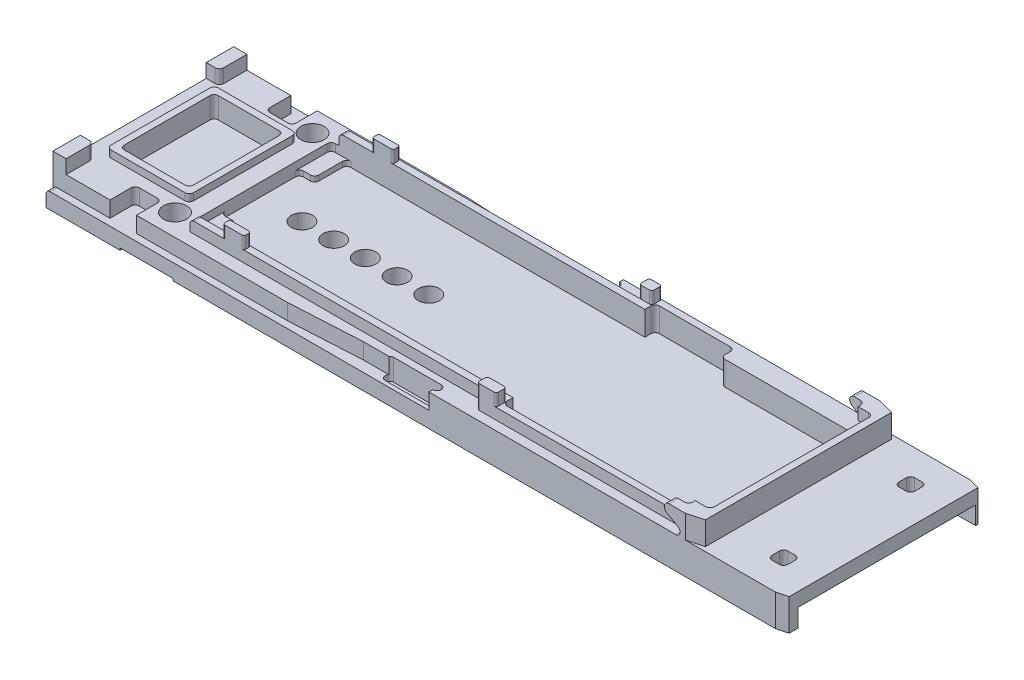
SolidWorks part; units mm, degrees
material "6063-T5"
ref_plane "Front Plane" through (0, 0, 0) normal (0, 0, 1) x (1, 0, 0)
ref_plane "Top Plane" through (0, 0, 0) normal (0, 1, 0) x (1, 0, 0)
ref_plane "Right Plane" through (0, 0, 0) normal (1, 0, 0) x (0, 0, -1)
sketch "Sketch1" plane through (0, 0, 0) normal (0, 1, 0) x (1, 0, 0)
  line L1 (-35, 9.2) -> (35, 9.2)
  line L2 (-35, 9.2) -> (-35, -9.2)
  line L3 (-35, -9.2) -> (35, -9.2)
  line L4 (35, 9.2) -> (35, -9.2)
  line L5 (-35, 9.2) -> (35, -9.2) construction
  line L6 (-35, -9.2) -> (35, 9.2) construction
  point P0 (0, 0)
  dimension "D1" = 70
  dimension "D2" = 18.4
extrude "Boss-Extrude1" add sketch "Sketch1" along normal blind 4.05
sketch "Sketch2" plane through (0, 4.05, 0) normal (0, 1, 0) x (1, 0, 0)
  line L0 (-35, 9.2) -> (-35, -9.2) construction
  line L1 (-23.95, 6.725) -> (-23.95, -6.725)
  line L2 (-23.95, -6.725) -> (6.7, -6.725)
  line L3 (6.7, -6.725) -> (6.7, -7.7)
  line L4 (6.7, -7.7) -> (26.3, -7.7)
  line L6 (26.3, -7.7) -> (26.3, 7.7)
  line L7 (26.3, 7.7) -> (5.7, 7.7)
  line L8 (5.7, 7.7) -> (5.7, 6.725)
  line L9 (5.7, 6.725) -> (-23.95, 6.725)
  line L10 (0, 0) -> (26.3, 0) construction
  dimension "D1" = 13.45
  dimension "D2" = 15.4
  dimension "D3" = 20.6
  dimension "D4" = 50.25
  dimension "D5" = 11.05
  dimension "D6" = 19.6
extrude "Cut-Extrude1" cut sketch "Sketch2" against normal blind 2.28
sketch "Sketch5" plane through (0, 4.05, 0) normal (0, 1, 0) x (1, 0, 0)
  line L0 (-23.95, 0) -> (-35, 0) construction
  line L1 (-32.75, 4.45) -> (-26.2, 4.45)
  line L2 (-32.75, 4.45) -> (-32.75, -4.45)
  line L3 (-32.75, -4.45) -> (-26.2, -4.45)
  line L4 (-26.2, 4.45) -> (-26.2, -4.45)
  line L5 (-32.75, 4.45) -> (-26.2, -4.45) construction
  line L6 (-32.75, -4.45) -> (-26.2, 4.45) construction
  line L7 (-23.95, 6.725) -> (-23.95, -6.725) construction
  line L8 (-35, 9.2) -> (-35, -9.2) construction
  point P0 (-29.475, 0)
  dimension "D1" = 8.9
  dimension "D2" = 6.55
extrude "Cut-Extrude2" cut sketch "Sketch5" against normal blind 2.38
sketch "Sketch17" plane through (0, 4.05, 0) normal (0, 1, 0) x (1, 0, 0)
  line L0 (-35, -9.2) -> (35, -9.2) construction
  line L1 (35, 9.2) -> (35, -9.2)
  line L2 (0, 0) -> (26.95, 0) construction
  line L4 (26.3, -7.7) -> (26.3, 7.7) construction
  line L5 (5.7, 7.7) -> (5.7, 6.725) construction
  line L11 (-35, 9.2) -> (35, 9.2)
  line L12 (-35, 9.2) -> (-35, -9.2)
  line L13 (-35, -9.2) -> (35, -9.2)
  line L14 (-23.2, 7.375) -> (-23.2, -7.375)
  line L57 (-23.2, -7.375) -> (5.05, -7.375)
  line L58 (5.05, -7.375) -> (5.05, -8.325)
  line L59 (5.05, -8.325) -> (26.95, -8.325)
  line L60 (26.95, -8.325) -> (26.95, 8.325)
  line L61 (26.95, 8.325) -> (5.05, 8.325)
  line L62 (5.05, 8.325) -> (5.05, 7.375)
  line L63 (5.05, 7.375) -> (-23.2, 7.375)
  dimension "D1" = 11.8
  dimension "D2" = 7.375
  dimension "D3" = 8.325
  dimension "D4" = 0.65
  dimension "D5" = 0.65
extrude "Cut-Extrude8" cut sketch "Sketch17" against normal blind 1.05
sketch "Sketch18" plane through (0, 0, 0) normal (0, 1, 0) x (1, 0, 0)
  line L10 (-32.75, 4.45) -> (-26.2, 4.45) construction
  line L11 (-26.2, -4.45) -> (-26.2, 4.45) construction
  line L12 (-32.75, -4.45) -> (-26.2, -4.45) construction
  line L13 (-32.75, 4.45) -> (-32.75, -4.45) construction
  line L14 (-33.375, 5.075) -> (-33.375, -5.075)
  line L15 (-33.375, -5.075) -> (-25.575, -5.075)
  line L16 (-25.575, -5.075) -> (-25.575, 5.075)
  line L17 (-25.575, 5.075) -> (-33.375, 5.075)
  line L18 (-33.375, 5.075) -> (-33.375, -5.075)
  line L19 (-33.375, -5.075) -> (-25.575, -5.075)
  line L20 (-25.575, -5.075) -> (-25.575, 5.075)
  line L21 (-25.575, 5.075) -> (-33.375, 5.075)
  line L22 (-32.75, 4.45) -> (-26.2, 4.45)
  line L23 (-26.2, -4.45) -> (-26.2, 4.45)
  line L24 (-32.75, -4.45) -> (-26.2, -4.45)
  line L25 (-32.75, 4.45) -> (-32.75, -4.45)
  dimension "D1" = 0.625
extrude "Boss-Extrude3" add sketch "Sketch18" along normal blind 3.67
hole_wizard "CSK for M2 Countersunk Flat Head Screw1" positions "Sketch7" profile "Sketch6" countersink size "M2" standard "ISO" end condition through all
sketch "Sketch7" plane through (-7.9019, 0, 3.8056) normal (0, 1, 0) x (-1, 0, 0)
  line L0 (-7.9019, -3.8056) -> (27.0981, -3.8056) construction
  line L1 (27.0981, -13.0056) -> (27.0981, 5.3944) construction
  line L4 (27.0981, 5.3944) -> (27.0981, -13.0056) construction
  point P0 (17.5981, -10.3056)
  point P1 (17.5981, 2.6944)
  dimension "D1" = 13
  dimension "D2" = 9.5
sketch "Sketch6" plane through (-25.5, 0, -6.5) normal (1, 0, 0) x (0, 0, -1)
  line L0 (0, 0) -> (0, 4.05)
  line L1 (0, 4.05) -> (1.1, 4.05)
  line L2 (1.1, 4.05) -> (1.1, 1.3)
  line L3 (1.1, 1.3) -> (2.2, 0.2)
  line L4 (2.2, 0.2) -> (2.2, 0)
  line L6 (2.2, 0) -> (0, 0)
  line L7 (-1.1, 1.3) -> (-2.2, 0.2) construction
  line L11 (0, -6.35) -> (0, 107.95) construction
  dimension "Thru Hole Dia." = 2.2
  dimension "Thru Hole Depth" = 4.05
  dimension "C'Sink Dia." = 4.4
  dimension "C'Sink Angle" = 90
  dimension "Head Clearance" = 0.2
sketch "Sketch13" plane through (0, 4.05, 0) normal (0, 1, 0) x (1, 0, 0)
  line L0 (-35, 9.2) -> (1.2, 9.2)
  line L1 (35, 9.2) -> (35, -9.2) construction
  line L2 (1.2, 9.2) -> (1.2, 8.175)
  line L3 (1.2, 8.175) -> (-6, 8.175)
  line L4 (-6, 8.175) -> (-12.8, 8.55)
  line L5 (-12.8, 8.55) -> (-35, 8.55)
  line L6 (-35, 8.55) -> (-35, 9.2)
  line L10 (35, 9.2) -> (-35, 9.2) construction
  line L11 (-35, 9.2) -> (-35, -9.2) construction
  dimension "D1" = 8.175
  dimension "D2" = 33.8
  dimension "D3" = 7.2
  dimension "D4" = 6.8
  dimension "D5" = 0.65
extrude "Cut-Extrude5" cut sketch "Sketch13" against normal offset from surface (2.55 mm away) 1.5 up to face at (-25.5, 0, -8.7)
sketch "Sketch19" plane through (0, 0, 0) normal (0, 1, 0) x (1, 0, 0)
  line L1 (-35, 8.55) -> (-33.75, 8.55)
  line L2 (-35, 8.55) -> (-35, 5.95)
  line L3 (-35, 5.95) -> (-33.75, 5.95)
  line L4 (-33.75, 8.55) -> (-33.75, 5.95)
  dimension "D1" = 2.6
  dimension "D2" = 1.25
extrude "Boss-Extrude4" add sketch "Sketch19" along normal blind 4.3
sketch "Sketch20" plane through (0, 3, 0) normal (0, 1, 0) x (1, 0, 0)
  line L0 (-33.75, 8.55) -> (-12.8, 8.55) construction
  line L1 (-29.6, 8.55) -> (-27.1, 8.55)
  line L2 (-29.6, 8.55) -> (-29.6, 6.165)
  line L3 (-29.6, 6.165) -> (-27.1, 6.165)
  line L4 (-27.1, 8.55) -> (-27.1, 6.165)
  line L5 (-35, -9.2) -> (-35, 5.95) construction
  dimension "D1" = 2.5
  dimension "D2" = 6.165
  dimension "D3" = 5.4
extrude "Cut-Extrude9" cut sketch "Sketch20" against normal up to surface (1.5 mm away) up to face at (-14.4, 1.5, -8.6417)
sketch "Sketch21" plane through (0, 0, 0) normal (0, 1, 0) x (1, 0, 0)
  line L0 (5.05, 7.375) -> (-23.2, 7.375) construction
  line L1 (-20.1, 7.375) -> (-18.1, 7.375)
  line L2 (-20.1, 7.375) -> (-20.1, 6.725)
  line L3 (-20.1, 6.725) -> (-18.1, 6.725)
  line L4 (-18.1, 7.375) -> (-18.1, 6.725)
  line L5 (5.7, 6.725) -> (-23.95, 6.725) construction
  line L6 (-23.2, 7.375) -> (-23.2, 6.725) construction
  dimension "D1" = 2
  dimension "D2" = 5.1
extrude "Boss-Extrude5" add sketch "Sketch21" along normal blind 5.2
sketch "Sketch22" plane through (0, 0, 0) normal (0, -1, 0) x (1, 0, 0)
  line L0 (24.9, -7.7) -> (26.95, -7.7)
  line L1 (26.3, -7.7) -> (5.7, -7.7) construction
  line L2 (26.95, -8.325) -> (26.95, 8.325) construction
  line L3 (26.95, -7.7) -> (26.95, -9.2)
  line L4 (1.2, -9.2) -> (35, -9.2) construction
  line L5 (26.95, -9.2) -> (22.15, -9.2)
  line L6 (22.15, -9.2) -> (22.15, -8.325)
  line L7 (5.05, -8.325) -> (26.95, -8.325) construction
  line L8 (22.15, -8.325) -> (24.9, -8.325)
  line L9 (24.9, -8.325) -> (24.9, -7.7)
  dimension "D1" = 4.8
  dimension "D2" = 2.05
extrude "Boss-Extrude6" add sketch "Sketch22" against normal blind 5.2
chamfer "Chamfer2" distance 1.5 angle 15 1 edges at (26.95, 4.1, -9.2)
chamfer "Chamfer1" distance 1 angle 15 2 edges at (35, 1.5, -9.2) (35, 1.5, 9.2)
sketch "Sketch25" plane through (0, 3, 0) normal (0, 1, 0) x (1, 0, 0)
  line L1 (31.2, 6.75) -> (31.9, 6.75)
  line L2 (30.8, 6.35) -> (30.8, 5.65)
  line L3 (31.2, 5.25) -> (31.9, 5.25)
  line L4 (32.3, 6.35) -> (32.3, 5.65)
  line L5 (30.8, 6.75) -> (32.3, 5.25) construction
  line L6 (30.8, 5.25) -> (32.3, 6.75) construction
  line L7 (35, -8.9321) -> (35, 8.9321) construction
  arc A0 (31.9, 6.75) -> (32.3, 6.35) centre (31.9, 6.35) cw
  arc A1 (32.3, 5.65) -> (31.9, 5.25) centre (31.9, 5.65) cw
  arc A2 (31.2, 5.25) -> (30.8, 5.65) centre (31.2, 5.65) cw
  arc A3 (30.8, 6.35) -> (31.2, 6.75) centre (31.2, 6.35) cw
  point P0 (31.55, 6)
  dimension "D5" = 0.4
  dimension "D1" = 1.5
  dimension "D2" = 1.5
  dimension "D3" = 6
  dimension "D4" = 4.2
extrude "Cut-Extrude10" cut sketch "Sketch25" against normal through all
sketch "Sketch16" plane through (0, 0, 0) normal (0, -1, 0) x (1, 0, 0)
  line L0 (-28, -9.2) -> (-28, -6.5)
  line L2 (-23, -6.5) -> (-23, -9.2)
  line L3 (-23, -9.2) -> (-28, -9.2)
  line L4 (34, -9.2) -> (-35, -9.2) construction
  arc A0 (-28, -6.5) -> (-23, -6.5) centre (-25.5, -6.5) cw
  circle A1 centre (-25.5, -6.5) radius 2.2 construction
  dimension "D1" = 5
extrude "Cut-Extrude7" cut sketch "Sketch16" against normal blind 0.2
mirror "Mirror1" about plane through (0, 0, 0) normal (0, 0, 1) of "Cut-Extrude10", "Boss-Extrude5", "Cut-Extrude9", "Boss-Extrude4", "Cut-Extrude5", "Cut-Extrude7", "Boss-Extrude6", "Chamfer2"
sketch "Sketch29" plane through (0, 0, -9.2) normal (0, 0, 1) x (1, 0, 0)
  line L0 (23.6939, 4.3603) -> (24.7572, 3.7464)
  line L1 (24.6572, 3.7464) -> (23.6689, 4.317) construction
  line L2 (24.5572, 3) -> (21.5572, 3)
  line L3 (34, 3) -> (25.45, 3) construction
  line L5 (22.15, 5.2) -> (25.45, 5.2) construction
  line L6 (23.9189, 5.2) -> (21.5572, 5.2)
  line L7 (21.5572, 5.2) -> (21.5572, 3)
  arc A0 (24.7572, 3.7464) -> (24.5572, 3) centre (24.5572, 3.4) cw
  arc A1 (23.6939, 4.3603) -> (23.9189, 5.2) centre (23.9189, 4.75) cw
  arc A2 (23.9189, 5.25) -> (23.6689, 4.317) centre (23.9189, 4.75) ccw construction
  dimension "D2" = 3
  dimension "D1" = 0.4
extrude "Cut-Extrude12" cut sketch "Sketch29" along normal up to surface (0.875 mm away) up to face at (23.525, 4.625, -8.325)
sketch "Sketch30" plane through (0, 0, 9.2) normal (0, 0, 1) x (1, 0, 0)
  line L0 (23.6939, 4.3603) -> (24.7572, 3.7464)
  line L1 (24.5572, 3) -> (21.5572, 3)
  line L2 (22.15, 5.2) -> (25.45, 5.2) construction
  line L3 (23.9189, 5.2) -> (21.5572, 5.2)
  line L4 (21.5572, 5.2) -> (21.5572, 3)
  line L6 (1.2, 3) -> (22.15, 3) construction
  line L7 (24.7572, 3.7464) -> (24.2313, 4.05) construction
  arc A0 (24.7572, 3.7464) -> (24.5572, 3) centre (24.5572, 3.4) cw
  arc A1 (23.9189, 5.2) -> (23.6939, 4.3603) centre (23.9189, 4.75) ccw construction
  arc A2 (23.6939, 4.3603) -> (23.9189, 5.2) centre (23.9189, 4.75) cw
  dimension "D1" = 3
  dimension "D3" = 0.4
extrude "Cut-Extrude13" cut sketch "Sketch30" against normal up to surface (0.875 mm away) up to face at (23.525, 4.625, 8.325)
sketch "Sketch26" plane through (0, 0, 0) normal (0, -1, 0) x (1, 0, 0)
  line L0 (5.05, 7.375) -> (-23.2, 7.375) construction
  line L1 (6.7, 8.325) -> (4.9, 8.325)
  line L2 (6.7, 8.325) -> (6.7, 7.375)
  line L3 (6.7, 7.375) -> (4.9, 7.375)
  line L4 (4.9, 8.325) -> (4.9, 7.375)
  line L5 (5.05, -7.375) -> (-18.1, -7.375) construction
  line L6 (5.7, -8.325) -> (4.52, -8.325)
  line L7 (5.7, -8.325) -> (5.7, -7.375)
  line L8 (5.7, -7.375) -> (4.52, -7.375)
  line L9 (4.52, -8.325) -> (4.52, -7.375)
  line L10 (6.7, 6.725) -> (6.7, 7.7) construction
  line L12 (24.5572, 8.325) -> (5.05, 8.325) construction
  line L13 (5.7, -7.7) -> (5.7, -6.725) construction
  line L14 (5.05, -8.325) -> (24.5572, -8.325) construction
  dimension "D1" = 1.8
  dimension "D2" = 1.18
extrude "Boss-Extrude8" add sketch "Sketch26" against normal blind 5.2
fillet "Fillet1" radius 0.4 2 edges at (-23.2, 4.05, 7.05) (-23.2, 4.05, -7.05)
fillet "Fillet2" radius 0.2 16 edges at (-18.1, 4.625, -6.725) (-20.1, 4.625, -6.725) (-20.1, 4.625, -7.375) (-18.1, 4.625, -7.375) (-18.1, 4.625, 6.725) (-18.1, 4.625, 7.375) (-20.1, 4.625, 6.725) (-20.1, 4.625, 7.375) (5.7, 4.625, -7.375) (4.52, 4.625, -7.375) (5.7, 4.625, -8.325) (4.52, 4.1, -8.325) (6.7, 4.625, 8.325) (4.9, 4.1, 8.325) (4.9, 4.625, 7.375) (6.7, 4.625, 7.375)
sketch "Sketch23" plane through (0, 4.05, 0) normal (0, 1, 0) x (1, 0, 0)
  line L4 (26.3, 7.7) -> (26.3, -7.7)
  line L5 (26.3, -7.7) -> (26.95, -7.7)
  line L6 (26.95, -7.7) -> (26.95, 7.7)
  line L7 (26.95, 7.7) -> (26.3, 7.7)
  line L8 (26.3, 7.7) -> (26.3, -7.7)
  line L9 (26.3, -7.7) -> (26.95, -7.7)
  line L10 (26.95, -7.7) -> (26.95, 7.7)
  line L11 (26.95, 7.7) -> (26.3, 7.7)
  dimension "D1" = 0
extrude "Boss-Extrude7" add sketch "Sketch23" along normal up to surface (1.15 mm away) up to face at (25.284, 5.2, -8.464)
sketch "Sketch27" plane through (0, 1.77, 0) normal (0, 1, 0) x (1, 0, 0)
  line L0 (26.3, 7.7) -> (5.7, 7.7) construction
  line L1 (13.2, 7.7) -> (26.3, 7.7)
  line L2 (13.2, 7.7) -> (13.2, 6.425)
  line L3 (13.2, 6.425) -> (26.3, 6.425)
  line L4 (26.3, 7.7) -> (26.3, 6.425)
  line L5 (26.3, -7.7) -> (26.3, 7.7) construction
  line L6 (24.2313, 8.325) -> (5.5, 8.325) construction
  line L7 (5.7, 7.7) -> (5.7, 6.725) construction
  dimension "D1" = 1.9
  dimension "D2" = 7.5
extrude "Boss-Extrude9" add sketch "Sketch27" along normal up to surface (2.28 mm away) up to face at (-4.2057, 4.05, -7.2117)
fillet "Fillet3" radius 0.4 2 edges at (13.2, 2.91, -7.7) (13.2, 2.91, -6.425)
sketch "Sketch28" plane through (0, 0, 0) normal (0, -1, 0) x (1, 0, 0)
  line L1 (35, 8.1) -> (30.8, 8.1)
  line L2 (35, 8.1) -> (35, -8.7)
  line L3 (35, 0) -> (0, 0) construction
  line L4 (30.8, 8.1) -> (30.8, -7)
  line L5 (30.8, 6.35) -> (30.8, 5.65) construction
  line L6 (35, -8.7) -> (14.2, -8.7)
  line L8 (30.8, -7) -> (14.2, -7)
  line L9 (14.2, -8.7) -> (14.2, -7)
  line L10 (34, -9.2) -> (-23, -9.2) construction
  line L11 (35, 8.9321) -> (35, -8.9321) construction
  line L12 (-23, 9.2) -> (34, 9.2) construction
  dimension "D1" = 2.2
  dimension "D2" = 0.5
  dimension "D3" = 1.1
  dimension "D4" = 16.6
extrude "Cut-Extrude11" cut sketch "Sketch28" against normal blind 1.7
sketch "Sketch31" plane through (0, 1.77, 0) normal (0, 1, 0) x (1, 0, 0)
  line L1 (-23.95, 6.725) -> (-22.5, 6.725)
  line L2 (-23.95, 6.725) -> (-23.95, 3.7)
  line L3 (-23.95, 3.7) -> (-22.5, 3.7)
  line L4 (-22.5, 6.725) -> (-22.5, 3.7)
  line L5 (-23.95, -6.725) -> (-22.5, -6.725)
  line L6 (-23.95, -6.725) -> (-23.95, -3.7)
  line L7 (-23.95, -3.7) -> (-22.5, -3.7)
  line L8 (-22.5, -6.725) -> (-22.5, -3.7)
  dimension "D1" = 7.4
  dimension "D2" = 1.45
extrude "Boss-Extrude10" add sketch "Sketch31" along normal blind 0.5
sketch "Sketch32" plane through (0, 1.5, 0) normal (0, 1, 0) x (1, 0, 0)
  line L1 (1.2, 8.175) -> (-3.3, 8.175)
  line L2 (1.2, 8.175) -> (1.2, 8.825)
  line L3 (1.2, 8.825) -> (-3.3, 8.825)
  line L4 (-3.3, 8.175) -> (-3.3, 8.825)
  line L5 (1.2, -8.175) -> (-3.3, -8.175)
  line L6 (1.2, -8.175) -> (1.2, -8.825)
  line L7 (1.2, -8.825) -> (-3.3, -8.825)
  line L8 (-3.3, -8.175) -> (-3.3, -8.825)
  dimension "D1" = 4.5
  dimension "D2" = 0.65
extrude "Cut-Extrude14" cut sketch "Sketch32" against normal blind 0.55
sketch "Sketch33" plane through (0, 0.95, 0) normal (0, 1, 0) x (1, 0, 0)
  line L1 (-3.3, -8.825) -> (1.2, -8.825)
  line L2 (1.2, -8.175) -> (1.2, -9.2) construction
  line L3 (-3.3, -8.025) -> (1.2, -8.025)
  arc A0 (-3.3, -8.025) -> (-3.3, -8.825) centre (-3.3, -8.425) ccw
  arc A1 (1.2, -8.025) -> (1.2, -8.825) centre (1.2, -8.425) cw
  dimension "D1" = 0.8
extrude "Cut-Extrude15" cut sketch "Sketch33" along normal through all
mirror "Mirror2" about plane through (0, 0, 0) normal (0, 0, 1) of "Cut-Extrude15"
fillet "Fillet5" radius 0.4 24 edges at (30.8, 0.85, 8.1) (14.2, 0.85, -8.7) (14.2, 0.85, -7) (6.7, 2.91, 7.7) (26.3, 3.485, 7.7) (24.9, 4.625, 8.325) (24.9, 4.625, -8.325) (26.3, 4.625, -7.7) (26.3, 2.91, -6.425) (5.7, 2.91, -7.7) (-23.95, 2.635, 6.725) (-22.5, 2.02, 6.725) (-23.95, 2.02, 3.7) (-23.95, 2.02, -3.7) (-22.5, 2.02, -6.725) (-23.95, 2.635, -6.725) (-26.2, 2.67, 4.45) (-32.75, 2.67, 4.45) (-32.75, 2.67, -4.45) (-26.2, 2.67, -4.45) (-27.1, 2.25, -6.165) (-29.6, 2.25, -6.165) (-27.1, 2.25, 6.165) (-29.6, 2.25, 6.165)
fillet "Fillet6" radius 0.4 2 edges at (-22.5, 2.02, -3.7) (-22.5, 2.02, 3.7)
fillet "Fillet7" radius 0.4 2 edges at (-35, 1.5, 8.875) (-35, 1.5, -8.875)
fillet "Fillet8" radius 0.4 6 edges at (-33.75, 3.65, -5.95) (-33.75, 3.65, 5.95) (-33.375, 3.335, -5.075) (-25.575, 3.335, -5.075) (-33.375, 3.335, 5.075) (-25.575, 3.335, 5.075)
sketch "Sketch34" plane through (0, 1.77, 0) normal (0, 1, 0) x (1, 0, 0)
  circle A0 centre (-20, 0) radius 1
  dimension "D1" = 2
  dimension "D2" = 20
extrude "Cut-Extrude16" cut sketch "Sketch34" against normal through all
pattern_linear "LPattern1" count 5 spacing 3 along (1, 0, 0) of "Cut-Extrude16"
